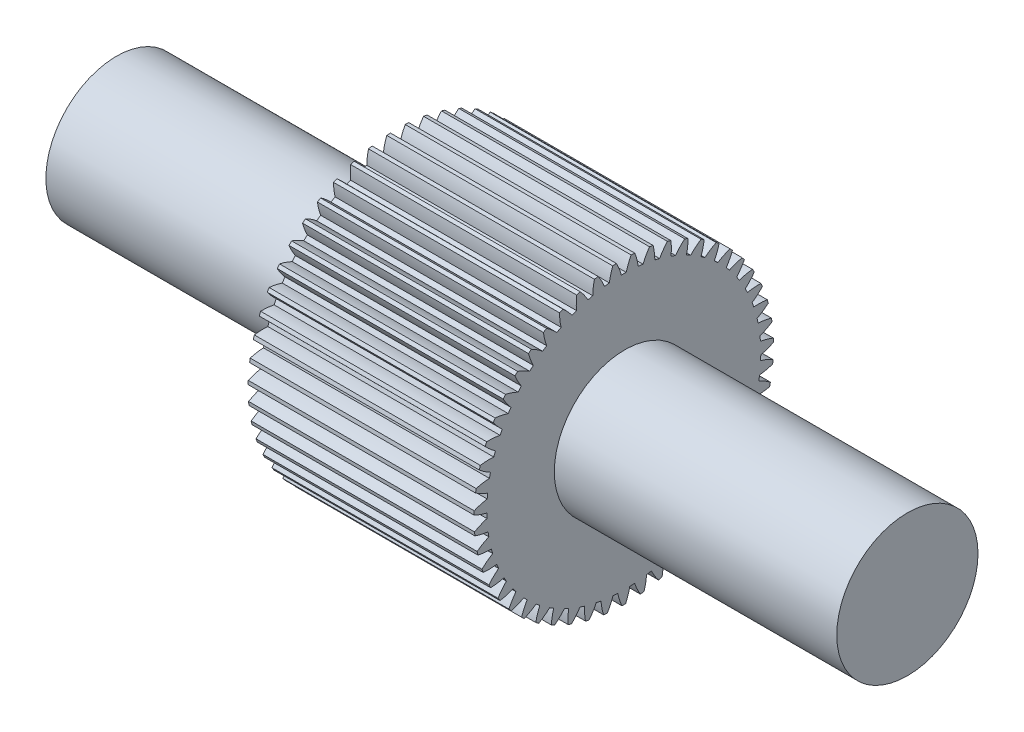
SolidWorks part; units mm, degrees
ref_plane "Plane1" through (0, 0, 0) normal (0, 0, 1) x (1, 0, 0)
ref_plane "Plane2" through (0, 0, 0) normal (0, 1, 0) x (1, 0, 0)
ref_plane "Plane3" through (0, 0, 0) normal (1, 0, 0) x (0, 0, -1)
sketch "HoldingSke" plane through (0, 0, 0) normal (0, 1, 0) x (1, 0, 0)
  line L0 (0, 0) -> (0.3147, -0.3886)
  line L1 (-15, 0) -> (100, 0) construction
  line L2 (0, 0) -> (-2.1039, 2.3779)
  line L3 (0, 0) -> (-11.863, 4.5341)
  line L4 (0, 0) -> (5.4348, 6.7114)
  line L5 (0, 0) -> (-46.8476, -17.4728)
  line L6 (0, 0) -> (-66.317, -44.7443)
  line L7 (-2.1039, 2.3779) -> (15.1161, 80.5027)
  line L8 (-76.2, 54.61) -> (-76.1, 54.61)
  line L9 (-71.009, 38.7566) -> (-53.1078, 45.2721)
  line L10 (-76.2, 71.12) -> (104.1128, 71.12)
  line L11 (0, 0) -> (-80, 0)
  line L12 (-76.2, 101.6) -> (-76.133, 101.6)
  line L13 (24.9733, 27.94) -> (52.9518, 28.4284)
  line L14 (24.9733, 27.94) -> (24.9743, 27.94)
  line L15 (24.9733, 27.94) -> (100.4006, 29.5858)
  line L16 (-63.627, -2) -> (-12.827, -2)
  circle A0 centre (0, 0) radius 0.4
  circle A1 centre (0, 0) radius 37.5
  circle A2 centre (0, 0) radius 37.5
  circle A3 centre (0, 0) radius 0.4
  dimension "Num_teeth" = 51
  dimension "Pitch_radius" = 180.3128
  dimension "Width" = 80
  dimension "Thickness" = 80
sketch "BasProSke" plane through (0, 0, 0) normal (0, 1, 0) x (1, 0, 0)
  line L0 (-10, 0) -> (60, 0) construction
  line L1 (0, 0) -> (0, 53)
  line L2 (0, 0) -> (80, 0)
  line L3 (80, 0) -> (80, 53)
  line L4 (80, 53) -> (0, 53)
  dimension "Thickness" = 80
  dimension "Diameter" = 106
revolve "Base-Revolve" add sketch "BasProSke" angle 360 about L0
sketch "TooCutSke" plane through (0, 0, 0) normal (1, 0, 0) x (0, 0, -1)
  line L1 (0, 0) -> (0, 107) construction
  line L2 (0, 0) -> (-1.6878, 50.9721) construction
  line L3 (0, 0) -> (-6.2767, 101.7652) construction
  line L4 (-1.6878, 50.9721) -> (-3.1383, 50.8826) construction
  arc A0 (0.8589, 48.4914) -> (-0.8589, 48.4914) centre (0, 0) ccw
  arc A1 (2.6252, 52.9604) -> (-2.6252, 52.9604) centre (0, 0) ccw
  circle A2 centre (0, 0) radius 51 construction
  circle A3 centre (0, 0) radius 47.9243 construction
  arc A4 (-0.8589, 48.4914) -> (-2.6252, 52.9604) centre (-20.5819, 43.2796) ccw
  arc A5 (2.6252, 52.9604) -> (0.8589, 48.4914) centre (20.5819, 43.2796) ccw
extrude "ToothCut" cut sketch "TooCutSke" along normal through all
fillet "Breaks" [suppressed] radius 0.04 tangent propagation no
fillet "RootFillets" [suppressed] radius 0.501
pattern_circular "TeethCuts" count 51 every 7.059 about axis through (-10, 0, 0) along (1, 0, 0) of "ToothCut", "RootFillets", "Breaks"
sketch "HubNeaOneSke" plane through (0, 0, 0) normal (-1, 0, 0) x (0, 0, 1)
  circle A0 centre (0, 0) radius 37.5
  dimension "Diameter" = 75
extrude "HubNearOne" [suppressed] add sketch "HubNeaOneSke" along normal blind 20.0001
sketch "HubNeaBotSke" plane through (0, 0, 0) normal (-1, 0, 0) x (0, 0, 1)
  circle A0 centre (0, 0) radius 37.5
  dimension "Diameter" = 75
extrude "HubNearBoth" [suppressed] add sketch "HubNeaBotSke" along normal blind 10
ref_plane "FarPln" through (80, 0, 0) normal (1, 0, 0) x (0, 0, -1)
sketch "HubFarSke" plane through (80, 0, 0) normal (1, 0, 0) x (0, 0, -1)
  circle A0 centre (0, 0) radius 37.5
  dimension "Diameter" = 75
extrude "HubFar" [suppressed] add sketch "HubFarSke" along normal blind 10
sketch "BorSke" plane through (0, 0, 0) normal (1, 0, 0) x (0, 0, -1)
  circle A0 centre (0, 0) radius 0.4
  dimension "Diameter" = 0.8
extrude "Bore" cut sketch "BorSke" along normal mid plane 160.0001
sketch "KeySke" plane through (0, 0, 0) normal (1, 0, 0) x (0, 0, -1)
  line L0 (-0.05, 0) -> (-0.05, 0.5)
  line L1 (-0.05, 0.5) -> (0.05, 0.5)
  line L2 (0.05, 0.5) -> (0.05, 0)
  line L3 (0, 0) -> (0, 34) construction
  line L4 (-0.05, 0) -> (0.05, 0)
extrude "Keyway" [suppressed] cut sketch "KeySke" along normal mid plane 160.0001
pattern_circular "Keyway2" [suppressed] count 2 every 90 about axis through (-10, 0, 0) along (1, 0, 0) reverse direction yes
sketch "草圖2" plane through (80, 0, 0) normal (1, 0, 0) x (0, 0, -1)
  circle A0 centre (0.4, 0) radius 25
  circle A1 centre (0, 0) radius 0.4 construction
  dimension "D1" = 50
extrude "填料-伸長1" add sketch "草圖2" along normal blind 100
extrude "填料-伸長2" add sketch "草圖2<2>" against normal blind 100 from surface starting at face at (0, 0, -0.4)
sketch "草圖2<2>" plane through (80, 0, 0) normal (1, 0, 0) x (0, 0, -1) same geometry as "草圖2"
equation "' \"Module@HoldingSke\" = 6.35"
equation "' \"Num_teeth@HoldingSke\" = 12"
equation "' \"Ap@HoldingSke\" =  20"
equation "' \"Ap@HoldingSke\" = 20"
equation "' \"Width@HoldingSke\" = 0.5 * 25.4"
equation "' \"Hub_dia@HoldingSke\"= 1 * 25.4"
equation "' \"Hub_dia@HoldingSke\" = 1 * 25.4"
equation "' \"Overall_len@HoldingSke\" = 1.0 * 25.4"
equation "' \"Bore@HoldingSke\" = 0.75 * 25.4"
equation "' \"T_dim@HoldingSke\" = 0.1 * 25.4"
equation "' \"Width@KeySke\" = 0.25 * 25.4"
equation "' \"Show_teeth@HoldingSke\" = 13"
equation "' \"Backlash@HoldingSke\" = 0.009 * 25.4"
equation "' \"Addendum_fac@HoldingSke\" = 1.0"
equation "' \"Dedendum_fac@HoldingSke\" = 1.25"
equation "' \"Dedendum_add@HoldingSke\" = 0.00005 * 25.4"
equation "' \"Clearance_fac@HoldingSke\" = 0.25"
equation "\"Pitch@HoldingSke\" = 1 / \"Module@HoldingSke\""
equation "\"Overcut_dia@TooCutSke\" = (\"Num_teeth@HoldingSke\" + 2 * \"Addendum_fac@HoldingSke\") / \"Pitch@HoldingSke\" + 0.002 * 25.4"
equation "\"Pitch_dia@TooCutSke\" = \"Num_teeth@HoldingSke\" / \"Pitch@HoldingSke\""
equation "\"Base_dia@TooCutSke\" = \"Num_teeth@HoldingSke\" / \"Pitch@HoldingSke\" * cos((\"Ap@HoldingSke\"  * 3.14159265 / 180))"
equation "\"Root_dia@TooCutSke\" = (\"Num_teeth@HoldingSke\" + 2) / \"Pitch@HoldingSke\" - 2 * (\"Addendum_fac@HoldingSke\" + \"Dedendum_fac@HoldingSke\") / \"Pitch@HoldingSke\" - \"Dedendum_add@HoldingSke\" * 2"
equation "\"Half_ang@TooCutSke\" = 180 / \"Num_teeth@HoldingSke\""
equation "\"Half_CT@TooCutSke\" = \"Num_teeth@HoldingSke\" / \"Pitch@HoldingSke\" * sin((3.14159265 / 2 / \"Num_teeth@HoldingSke\")) / 2 - 7 * \"Backlash@HoldingSke\" / 4"
equation "\"Flank_rad@TooCutSke\" = \"Num_teeth@HoldingSke\" / \"Pitch@HoldingSke\" / 5"
equation "\"Radius@RootFillets\" = \"Clearance_fac@HoldingSke\" / \"Pitch@HoldingSke\" + \"Dedendum_add@HoldingSke\""
equation "\"Break_rad@Breaks\" = 0.02 / \"Pitch@HoldingSke\""
equation "\"Thickness@HoldingSke\" = \"Width@HoldingSke\""
equation "\"OAL@HoldingSke\" = \"Thickness@HoldingSke\""
equation "\"MHD@HoldingSke\" = (\"Num_teeth@HoldingSke\" + 2) / \"Pitch@HoldingSke\" - 2 * (\"Addendum_fac@HoldingSke\" + \"Dedendum_fac@HoldingSke\")  / \"Pitch@HoldingSke\" - \"Dedendum_add@HoldingSke\" * 2"
equation "\"MBD@HoldingSke\" = (\"Num_teeth@HoldingSke\" + 2) / \"Pitch@HoldingSke\" - 2 * (\"Addendum_fac@HoldingSke\" + \"Dedendum_fac@HoldingSke\")  / \"Pitch@HoldingSke\" - \"Dedendum_add@HoldingSke\" * 2 - 0.002 * 25.4"
equation "\"MHD@HoldingSke\" = ((sgn( \"MHD@HoldingSke\" - \"Hub_dia@HoldingSke\" )-1)*( \"MHD@HoldingSke\" - \"Hub_dia@HoldingSke\" ))/-2+ \"Hub_dia@HoldingSke\""
equation "\"MBD@HoldingSke\" = ((sgn( \"MBD@HoldingSke\" - \"Bore@HoldingSke\" )-1)*( \"MBD@HoldingSke\" - \"Bore@HoldingSke\" ))/-2+ \"Bore@HoldingSke\""
equation "\"OAL@HoldingSke\" = ((sgn( \"OAL@HoldingSke\" - \"Overall_len@HoldingSke\" )+1)*( \"OAL@HoldingSke\" - \"Overall_len@HoldingSke\" ))/2 + \"Overall_len@HoldingSke\" + 0.000002 * 25.4"
equation "\"Num_teeth@TeethCuts\" = int( \"Show_teeth@HoldingSke\" ) + 1"
equation "\"Num_teeth@TeethCuts\" = ((sgn( \"Num_teeth@TeethCuts\" - \"Num_teeth@HoldingSke\" )-1)*( \"Num_teeth@TeethCuts\" - \"Num_teeth@HoldingSke\" ))/-2+ \"Num_teeth@HoldingSke\""
equation "\"Num_teeth@TeethCuts\" = ((sgn( \"Num_teeth@TeethCuts\" - 2.0)+1)*( \"Num_teeth@TeethCuts\" - 2.0))/2 +2.0"
equation "\"Angle@TeethCuts\" = 360.0 / \"Num_teeth@HoldingSke\""
equation "\"Diameter@BasProSke\" = (\"Num_teeth@HoldingSke\" + 2 * \"Addendum_fac@HoldingSke\") / \"Pitch@HoldingSke\""
equation "\"Thickness@BasProSke\"  = \"Thickness@HoldingSke\""
equation "' \"Fillet_rad@BasProSke\" =  \"Thickness@HoldingSke\" * 0.05"
equation "' \"Fillet_rad@BasProSke\" = \"Thickness@HoldingSke\" * 0.05"
equation "\"MHD@HoldingSke\" = ((sgn( \"MHD@HoldingSke\" - \"Root_dia@TooCutSke\" )-1)*( \"MHD@HoldingSke\" - \"Root_dia@TooCutSke\" ))/-2+ \"Root_dia@TooCutSke\""
equation "\"Diameter@HubNeaOneSke\" = \"MHD@HoldingSke\""
equation "\"Length@HubNearOne\" = \"OAL@HoldingSke\" - \"Thickness@BasProSke\""
equation "\"Diameter@HubNeaBotSke\" = \"MHD@HoldingSke\""
equation "\"Length@HubNearBoth\" = ( \"OAL@HoldingSke\" - \"Thickness@BasProSke\" ) / 2.0"
equation "\"Thickness@FarPln\" = \"Thickness@BasProSke\""
equation "\"Diameter@HubFarSke\" = \"MHD@HoldingSke\""
equation "\"Length@HubFar\" = ( \"OAL@HoldingSke\" - \"Thickness@BasProSke\" ) / 2.0"
equation "\"Diameter@BorSke\" = \"MBD@HoldingSke\""
equation "\"D1@Bore\" = \"OAL@HoldingSke\" * 2.0"
equation "\"D1@Keyway\" = \"OAL@HoldingSke\" * 2.0"
equation "\"Offset@KeySke\" = \"T_dim@HoldingSke\" + \"MBD@HoldingSke\" / 2.0"
